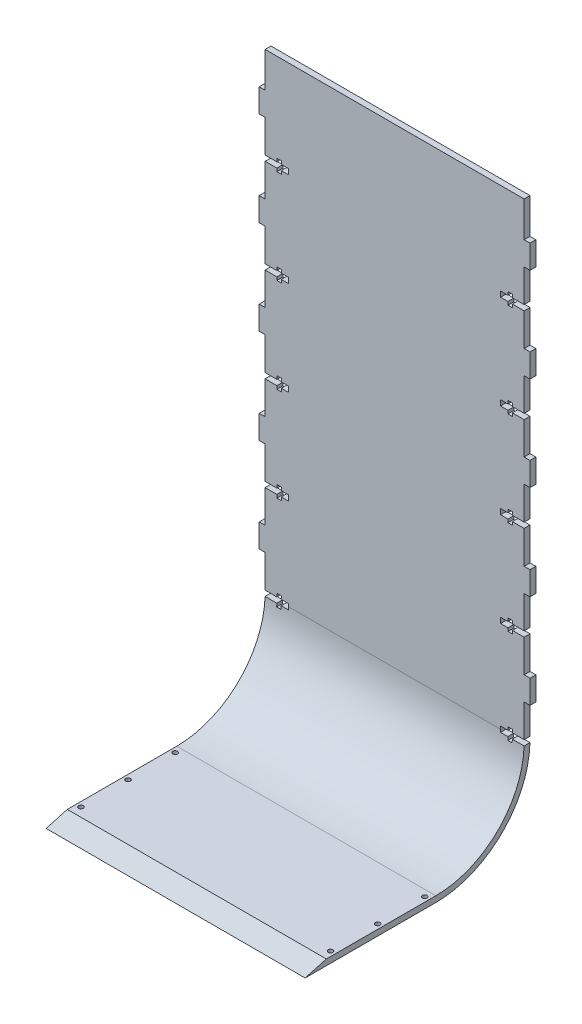
SolidWorks part; units mm, degrees
ref_plane "Front Plane" through (0, 0, 0) normal (0, 0, 1) x (1, 0, 0)
ref_plane "Top Plane" through (0, 0, 0) normal (0, 1, 0) x (1, 0, 0)
ref_plane "Right Plane" through (0, 0, 0) normal (1, 0, 0) x (0, 0, -1)
sketch "Sketch1" plane through (0, 0, 0) normal (1, 0, 0) x (0, 0, -1)
  line L0 (-118.11, -50.8) -> (-106.68, -47.625)
  line L2 (0, 0) -> (0, 254)
  line L3 (0, 254) -> (3.175, 254)
  line L4 (3.175, 0) -> (3.175, 254)
  line L5 (-47.625, -50.8) -> (-118.11, -50.8)
  line L6 (-47.625, -47.625) -> (-106.68, -47.625)
  arc A0 (-47.625, -50.8) -> (3.175, 0) centre (-47.625, 0) ccw
  arc A1 (-47.625, -47.625) -> (0, 0) centre (-47.625, 0) ccw
  point P7 (0, 0)
  point P9 (0, 0)
  point P10 (0, 0)
  point P13 (0, 0)
extrude "Boss-Extrude1" add sketch "Sketch1" along normal blind 139.7 contours A1 L2 L3 L4 A0 L5 L0 L6
ref_plane "Plane1" through (69.85, 0, 0) normal (1, 0, 0) x (0, 0, -1)
sketch "Sketch4" plane through (0, 0, 0) normal (0, 0, 1) x (1, 0, 0)
  line L1 (0, 204.6605) -> (0, 201.7395)
  line L2 (0, 153.8605) -> (0, 150.9395)
  line L3 (0, 103.0605) -> (0, 100.1395)
  line L4 (0, 52.2605) -> (0, 49.3395)
  line L5 (0, 1.4605) -> (0, -1.4605)
  line L75 (6.35, 204.6605) -> (6.35, 206.375)
  line L76 (8.7312, 204.6605) -> (8.7312, 206.375)
  line L78 (0, 204.6605) -> (6.35, 204.6605)
  line L79 (12.7, 203.2) -> (12.7, 204.6605)
  line L80 (8.7312, 204.6605) -> (12.7, 204.6605)
  line L82 (0, 201.7395) -> (6.35, 201.7395)
  line L83 (12.7, 203.2) -> (12.7, 201.7395)
  line L84 (6.35, 200.025) -> (8.7312, 200.025)
  line L85 (6.35, 200.025) -> (6.35, 201.7395)
  line L86 (6.35, 206.375) -> (8.7312, 206.375)
  line L87 (8.7312, 200.025) -> (8.7312, 201.7395)
  line L88 (8.7312, 201.7395) -> (12.7, 201.7395)
  line L89 (8.7312, 153.8605) -> (12.7, 153.8605)
  line L90 (8.7312, 155.575) -> (8.7312, 153.8605)
  line L91 (6.35, 149.225) -> (8.7312, 149.225)
  line L92 (6.35, 155.575) -> (6.35, 153.8605)
  line L93 (6.35, 155.575) -> (8.7312, 155.575)
  line L94 (12.7, 152.4) -> (12.7, 153.8605)
  line L95 (0, 153.8605) -> (6.35, 153.8605)
  line L96 (8.7312, 150.9395) -> (12.7, 150.9395)
  line L97 (12.7, 152.4) -> (12.7, 150.9395)
  line L98 (0, 150.9395) -> (6.35, 150.9395)
  line L99 (8.7312, 150.9395) -> (8.7312, 149.225)
  line L100 (6.35, 150.9395) -> (6.35, 149.225)
  line L101 (6.35, 103.0605) -> (6.35, 104.775)
  line L102 (8.7312, 103.0605) -> (8.7312, 104.775)
  line L103 (0, 103.0605) -> (6.35, 103.0605)
  line L104 (12.7, 101.6) -> (12.7, 103.0605)
  line L105 (8.7312, 103.0605) -> (12.7, 103.0605)
  line L106 (0, 100.1395) -> (6.35, 100.1395)
  line L107 (12.7, 101.6) -> (12.7, 100.1395)
  line L108 (6.35, 98.425) -> (8.7312, 98.425)
  line L109 (6.35, 98.425) -> (6.35, 100.1395)
  line L110 (6.35, 104.775) -> (8.7312, 104.775)
  line L111 (8.7312, 98.425) -> (8.7312, 100.1395)
  line L112 (8.7312, 100.1395) -> (12.7, 100.1395)
  line L113 (8.7312, 52.2605) -> (12.7, 52.2605)
  line L114 (8.7312, 53.975) -> (8.7312, 52.2605)
  line L115 (6.35, 47.625) -> (8.7312, 47.625)
  line L116 (6.35, 53.975) -> (6.35, 52.2605)
  line L117 (6.35, 53.975) -> (8.7312, 53.975)
  line L118 (12.7, 50.8) -> (12.7, 52.2605)
  line L119 (0, 52.2605) -> (6.35, 52.2605)
  line L120 (8.7312, 49.3395) -> (12.7, 49.3395)
  line L121 (12.7, 50.8) -> (12.7, 49.3395)
  line L122 (0, 49.3395) -> (6.35, 49.3395)
  line L123 (8.7312, 49.3395) -> (8.7312, 47.625)
  line L124 (6.35, 49.3395) -> (6.35, 47.625)
  line L125 (6.35, 1.4605) -> (6.35, 3.175)
  line L126 (8.7312, 1.4605) -> (8.7312, 3.175)
  line L127 (0, 1.4605) -> (6.35, 1.4605)
  line L128 (12.7, 0) -> (12.7, 1.4605)
  line L129 (8.7312, 1.4605) -> (12.7, 1.4605)
  line L130 (0, -1.4605) -> (6.35, -1.4605)
  line L131 (12.7, 0) -> (12.7, -1.4605)
  line L132 (6.35, -3.175) -> (8.7312, -3.175)
  line L133 (6.35, -3.175) -> (6.35, -1.4605)
  line L134 (6.35, 3.175) -> (8.7312, 3.175)
  line L135 (8.7312, -3.175) -> (8.7312, -1.4605)
  line L136 (8.7312, -1.4605) -> (12.7, -1.4605)
extrude "Cut-Extrude1" cut sketch "Sketch4" against normal blind 3.175 and the other way blind 3.175
sketch "Sketch5" plane through (0, 0, 0) normal (0, 0, 1) x (1, 0, 0)
  line L0 (0, 234.95) -> (0, 222.25)
  line L1 (0, 184.15) -> (0, 171.45)
  line L2 (0, 31.75) -> (0, 19.05)
  line L3 (0, 82.4354) -> (0, 69.7354)
  line L4 (0, 133.4646) -> (0, 120.7646)
  line L18 (0, 19.05) -> (-3.175, 19.05)
  line L20 (0, 31.75) -> (-3.175, 31.75)
  line L21 (-3.175, 19.05) -> (-3.175, 31.75)
  line L24 (-3.175, 82.4354) -> (-3.175, 69.7354)
  line L25 (0, 69.7354) -> (-3.175, 69.7354)
  line L27 (0, 82.4354) -> (-3.175, 82.4354)
  line L32 (0, 120.7646) -> (-3.175, 120.7646)
  line L34 (0, 133.4646) -> (-3.175, 133.4646)
  line L35 (-3.175, 120.7646) -> (-3.175, 133.4646)
  line L36 (-3.175, 184.15) -> (-3.175, 171.45)
  line L37 (0, 171.45) -> (-3.175, 171.45)
  line L39 (0, 184.15) -> (-3.175, 184.15)
  line L42 (0, 222.25) -> (-3.175, 222.25)
  line L44 (0, 234.95) -> (-3.175, 234.95)
  line L45 (-3.175, 222.25) -> (-3.175, 234.95)
extrude "Boss-Extrude2" add sketch "Sketch5" against normal blind 3.175
mirror "Mirror1" about plane through (69.85, 0, 0) normal (1, 0, 0) of "Cut-Extrude1", "Boss-Extrude2"
sketch "Sketch8" plane through (0, -47.625, 0) normal (0, 1, 0) x (1, 0, 0)
  circle A2 centre (2.54, -51.054) radius 1.27
  circle A3 centre (2.54, -76.454) radius 1.27
  circle A4 centre (2.54, -101.854) radius 1.27
extrude "Cut-Extrude2" cut sketch "Sketch8" against normal blind 3.175
mirror "Mirror2" about plane through (69.85, 0, 0) normal (1, 0, 0) of "Cut-Extrude2"
